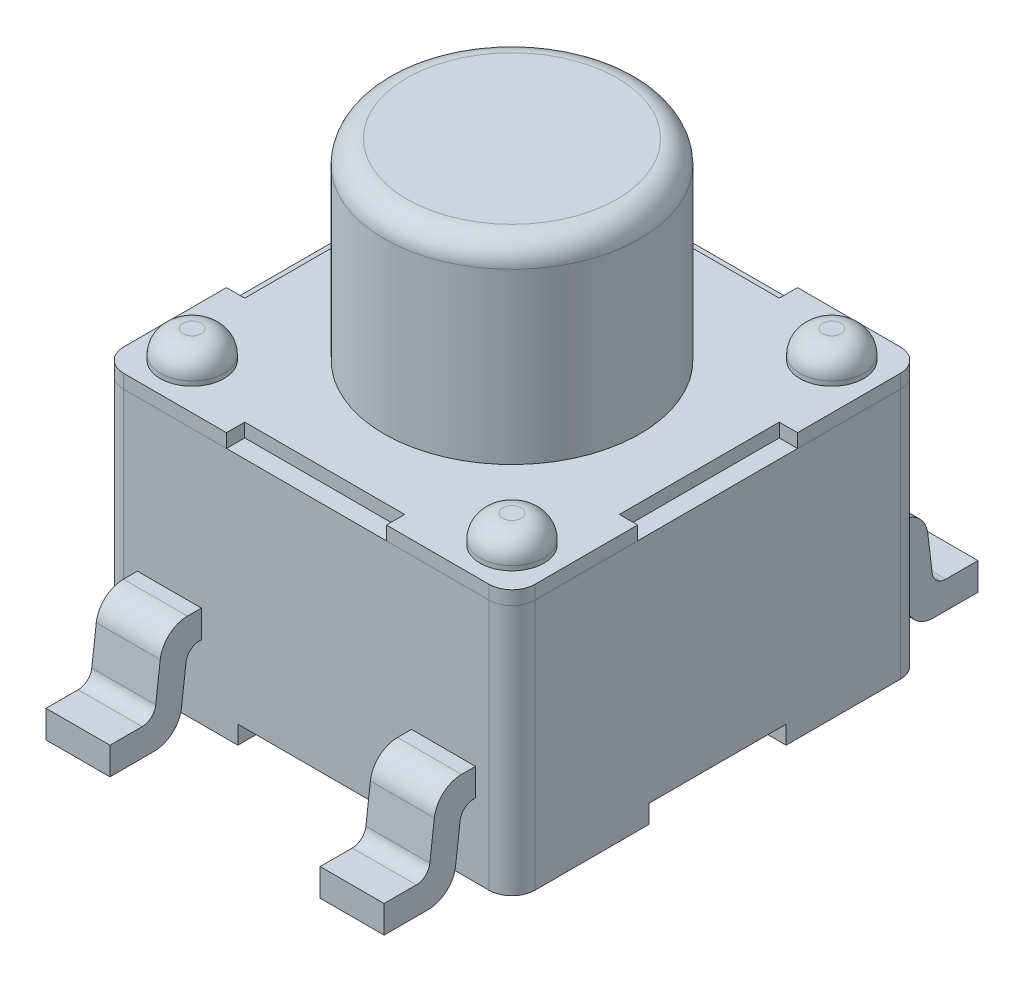
SolidWorks part; units mm, degrees
note: The reader was unsure of these and kept them because the rebuilt part matched: shared geometry of "Sketch5<4>".
ref_plane "Front Plane" through (0, 0, 0) normal (0, 0, 1) x (1, 0, 0)
ref_plane "Top Plane" through (0, 0, 0) normal (0, 1, 0) x (1, 0, 0)
ref_plane "Right Plane" through (0, 0, 0) normal (1, 0, 0) x (0, 0, -1)
sketch "Sketch1" plane through (0, 0, 0) normal (0, 1, 0) x (1, 0, 0)
  line L1 (-2, -2.25) -> (2, -2.25)
  line L2 (-2.25, -2) -> (-2.25, 2)
  line L3 (-2, 2.25) -> (2, 2.25)
  line L4 (2.25, -2) -> (2.25, 2)
  line L5 (-2.25, -2.25) -> (2.25, 2.25) construction
  line L6 (-2.25, 2.25) -> (2.25, -2.25) construction
  arc A0 (-2, -2.25) -> (-2.25, -2) centre (-2, -2) cw
  arc A1 (2, -2.25) -> (2.25, -2) centre (2, -2) ccw
  arc A2 (2, 2.25) -> (2.25, 2) centre (2, 2) cw
  arc A3 (-2.25, 2) -> (-2, 2.25) centre (-2, 2) cw
  point P0 (0, 0)
  dimension "D3" = 0.25
  dimension "D1" = 4.5
  dimension "D2" = 4.5
extrude "Boss-Extrude1" add sketch "Sketch1" along normal blind 2.75
sketch "Sketch4" plane through (0, 2.75, 0) normal (0, 1, 0) x (1, 0, 0)
  line L0 (0, 3.525) -> (0, -3.2696) construction
  line L1 (0.875, 2.25) -> (-0.875, 2.25)
  line L2 (0.875, 2.25) -> (0.875, 2.05)
  line L3 (0.875, 2.05) -> (-0.875, 2.05)
  line L4 (-2, -2.25) -> (2, -2.25)
  line L5 (2.25, -2) -> (2.25, 2)
  line L6 (2, 2.25) -> (-2, 2.25)
  line L7 (-2.25, 2) -> (-2.25, -2)
  line L8 (-2, -2.25) -> (2, -2.25)
  line L9 (2.25, -2) -> (2.25, 2)
  line L10 (2, 2.25) -> (-2, 2.25)
  line L11 (-2.25, 2) -> (-2.25, -2)
  line L12 (-0.875, 2.25) -> (-0.875, 2.05)
  line L13 (-2.25, 0.875) -> (-2.05, 0.875)
  line L14 (-2.25, 0.875) -> (-2.25, -0.875)
  line L15 (-2.25, -0.875) -> (-2.05, -0.875)
  line L16 (-2.05, 0.875) -> (-2.05, -0.875)
  line L17 (-0.875, -2.25) -> (0.875, -2.25)
  line L18 (-0.875, -2.25) -> (-0.875, -2.05)
  line L19 (-0.875, -2.05) -> (0.875, -2.05)
  line L20 (0.875, -2.25) -> (0.875, -2.05)
  line L21 (2.25, 0.875) -> (2.05, 0.875)
  line L22 (2.25, 0.875) -> (2.25, -0.875)
  line L23 (2.25, -0.875) -> (2.05, -0.875)
  line L24 (2.05, 0.875) -> (2.05, -0.875)
  line L25 (3.5717, 0) -> (-4.7244, 0) construction
  arc A4 (-2.25, -2) -> (-2, -2.25) centre (-2, -2) ccw
  arc A5 (2, -2.25) -> (2.25, -2) centre (2, -2) ccw
  arc A6 (2.25, 2) -> (2, 2.25) centre (2, 2) ccw
  arc A7 (-2, 2.25) -> (-2.25, 2) centre (-2, 2) ccw
  arc A8 (-2.25, -2) -> (-2, -2.25) centre (-2, -2) ccw
  arc A9 (2, -2.25) -> (2.25, -2) centre (2, -2) ccw
  arc A10 (2.25, 2) -> (2, 2.25) centre (2, 2) ccw
  arc A11 (-2, 2.25) -> (-2.25, 2) centre (-2, 2) ccw
  point P33 (0, -2.05)
  point P34 (2.05, 0)
  point P35 (0, 2.05)
  point P36 (-2.05, 0)
  dimension "D2" = 1.75
  dimension "D3" = 0.2
  dimension "D1" = 0
extrude "Boss-Extrude4" add sketch "Sketch4" along normal blind 0.15 separate body
sketch "Sketch2" plane through (0, 2.9, 0) normal (0, 1, 0) x (1, 0, 0)
  circle A0 centre (0, 0) radius 1.4
  dimension "D1" = 2.8
extrude "Boss-Extrude2" add sketch "Sketch2" along normal blind 2.1
fillet "Fillet1" radius 0.25 1 edges at (0, 5, 1.4)
sketch "Sketch3" plane through (0, 2.9, 0) normal (0, 1, 0) x (1, 0, 0)
  line L0 (2, 2.25) -> (-2, 2.25) construction
  line L1 (-2.25, 2) -> (-2.25, -2) construction
  line L2 (2.25, -2) -> (2.25, 2) construction
  line L3 (-2, -2.25) -> (2, -2.25) construction
  circle A0 centre (-1.75, -1.75) radius 0.35
  circle A1 centre (1.75, -1.75) radius 0.35
  circle A2 centre (1.75, 1.75) radius 0.35
  circle A3 centre (-1.75, 1.75) radius 0.35
  point P8 (0, 0)
  point P9 (0, 0)
  point P10 (0, 0)
  point P11 (0, 0)
  dimension "D1" = 0.7
  dimension "D2" = 0.5
  dimension "D3" = 0.5
  dimension "D4" = 0.5
  dimension "D5" = 0.5
extrude "Boss-Extrude3" add sketch "Sketch3" along normal blind 0.3
fillet "Fillet2" radius 0.25 1 edges at (1.75, 3.2, -1.4)
fillet "Fillet3" radius 0.25 1 edges at (-1.75, 3.2, -1.4)
fillet "Fillet4" radius 0.25 1 edges at (-1.75, 3.2, 2.1)
fillet "Fillet5" radius 0.25 1 edges at (1.75, 3.2, 2.1)
sketch "Sketch5" plane through (0, 0, 0) normal (-1, 0, 0) x (0, 0, 1)
  line L0 (2.25, 2.75) -> (2.25, 0) construction
  line L1 (2.25, 2.75) -> (2.25, 0)
  line L2 (-2.25, 2.75) -> (-2.25, 0) construction
  line L3 (-2.25, 2.75) -> (-2.25, 0)
  line L4 (2.25, 1.1) -> (2.4022, 1.1)
  line L5 (2.7, 0.836) -> (2.7489, 0.432)
  line L6 (2.8978, 0.3) -> (3.25, 0.3)
  line L7 (3.25, 0.3) -> (3.25, 0)
  line L8 (3.25, 0) -> (2.7649, 0)
  line L9 (2.4671, 0.264) -> (2.4182, 0.668)
  line L10 (2.2693, 0.8) -> (2.25, 0.8)
  line L11 (0, 5.5538) -> (0, -1.4448) construction
  line L12 (-2.2693, 0.8) -> (-2.25, 0.8)
  line L13 (-2.4671, 0.264) -> (-2.4182, 0.668)
  line L14 (-3.25, 0) -> (-2.7649, 0)
  line L15 (-3.25, 0.3) -> (-3.25, 0)
  line L16 (-2.8978, 0.3) -> (-3.25, 0.3)
  line L17 (-2.7, 0.836) -> (-2.7489, 0.432)
  line L18 (-2.25, 1.1) -> (-2.4022, 1.1)
  line L19 (-2.25, 2.75) -> (-2.25, 0)
  arc A0 (2.4182, 0.668) -> (2.2693, 0.8) centre (2.2693, 0.65) ccw
  arc A1 (2.7489, 0.432) -> (2.8978, 0.3) centre (2.8978, 0.45) ccw
  arc A2 (-2.2693, 0.8) -> (-2.4182, 0.668) centre (-2.2693, 0.65) ccw
  arc A3 (-2.8978, 0.3) -> (-2.7489, 0.432) centre (-2.8978, 0.45) ccw
  arc A4 (2.4022, 1.1) -> (2.7, 0.836) centre (2.4022, 0.8) cw
  arc A5 (2.7649, 0) -> (2.4671, 0.264) centre (2.7649, 0.3) cw
  arc A6 (-2.4671, 0.264) -> (-2.7649, 0) centre (-2.7649, 0.3) cw
  arc A7 (-2.7, 0.836) -> (-2.4022, 1.1) centre (-2.4022, 0.8) cw
  point P23 (0, 0)
  point P26 (2.4022, 0.8)
  point P29 (2.7649, 0.3)
  point P32 (-2.4022, 0.8)
  point P35 (-2.7649, 0.3)
  point P38 (2.6681, 1.1)
  point P41 (2.499, 0)
  point P44 (-2.499, 0)
  point P47 (-2.6681, 1.1)
  dimension "D6" = 0.15
  dimension "D7" = 0.3
  dimension "D1" = 1.1
  dimension "D2" = 0.3
  dimension "D3" = 0.3
  dimension "D4" = 0.3
  dimension "D5" = 6.5
extrude "Boss-Extrude5" add sketch "Sketch5" along normal blind 0.7 from offset 1.15 separate body contours A7 L17 A3 L16 L15 L14 A6 L13 A2 L12 L3 L18 | A5 L8 L7 L6 A1 L5 A4 L4 L1 L10 A0 L9 | L17 A7 L18 L3 L12 A2 L13 A6 L14 L15 L16 A3 | L8 A5 L9 A0 L10 L1 L4 A4 L5 A1 L6 L7
extrude "Boss-Extrude6" add sketch "Sketch5<4>" against normal blind 0.7 from offset 1.15 contours L8 A5 L9 A0 L10 L1 L4 A4 L5 A1 L6 L7 | L17 A7 L18 L3 L12 A2 L13 A6 L14 L15 L16 A3 offset against normal yes
sketch "Sketch5<4>" plane through (0, 0, 0) normal (-1, 0, 0) x (0, 0, 1) same geometry as "Sketch5"
sketch "Sketch7" plane through (0, 0, 0) normal (0, -1, 0) x (1, 0, 0)
  line L0 (-2.25, -2) -> (-2.25, 2) construction
  line L1 (-2.25, -0.75) -> (-0.75, -0.75)
  line L2 (-2.25, -0.75) -> (-2.25, 0.75)
  line L3 (-2.25, 0.75) -> (-0.75, 0.75)
  line L4 (2.25, -0.75) -> (2.25, 0.75)
  line L5 (2.25, 2) -> (2.25, -2) construction
  line L6 (-2, 2.25) -> (2, 2.25) construction
  line L7 (-0.75, 2.25) -> (0.75, 2.25)
  line L8 (-0.75, 2.25) -> (-0.75, 0.75)
  line L9 (-0.75, -2.25) -> (0.75, -2.25)
  line L10 (0.75, 2.25) -> (0.75, 0.75)
  line L11 (2, -2.25) -> (-2, -2.25) construction
  line L12 (-2.8489, 0) -> (3.1278, 0) construction
  line L13 (0, -3.9056) -> (0, 4.0933) construction
  line L14 (-0.75, -0.75) -> (-0.75, -2.25)
  line L15 (0.75, 0.75) -> (2.25, 0.75)
  line L16 (0.75, -0.75) -> (0.75, -2.25)
  line L17 (0.75, -0.75) -> (2.25, -0.75)
  point P21 (-2.25, 0)
  point P22 (2.25, 0)
  point P23 (0, -2.25)
  point P24 (0, 2.25)
  dimension "D1" = 1.5
extrude "Cut-Extrude1" cut sketch "Sketch7" against normal blind 0.2
